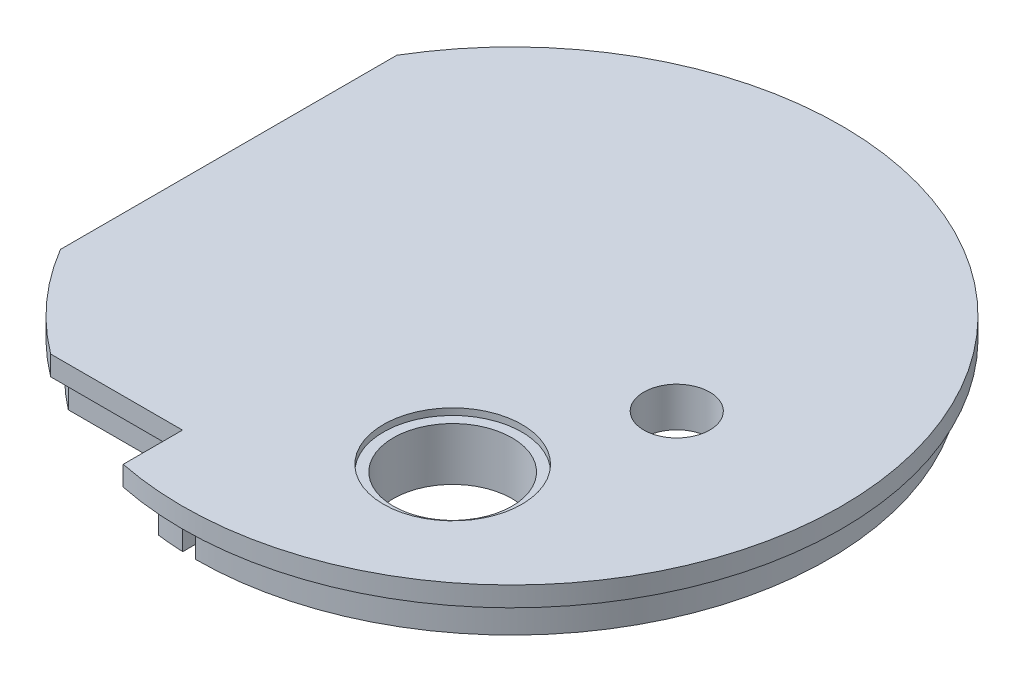
SolidWorks part; units mm, degrees
ref_plane "Front Plane" through (0, 0, 0) normal (0, 0, 1) x (1, 0, 0)
ref_plane "Top Plane" through (0, 0, 0) normal (0, 1, 0) x (1, 0, 0)
ref_plane "Right Plane" through (0, 0, 0) normal (1, 0, 0) x (0, 0, -1)
sketch "Sketch1" plane through (0, 0, 0) normal (0, 1, 0) x (1, 0, 0)
  line L0 (-43, 25.5147) -> (-43, -25.5147)
  line L1 (-30, -40) -> (-10, -40)
  line L2 (-10, -40) -> (-10, -48.9898)
  arc A0 (-43, -25.5147) -> (-30, -40) centre (0, 0) ccw
  arc A1 (-10, -48.9898) -> (-43, 25.5147) centre (0, 0) ccw
  dimension "D1" = 100
  dimension "D2" = 43
  dimension "D3" = 40
  dimension "D4" = 10
extrude "Boss-Extrude1" add sketch "Sketch1" along normal blind 3
sketch "Sketch2" plane through (0, 0, 0) normal (0, -1, 0) x (1, 0, 0)
  line L0 (-40.9781, 24.9959) -> (-40.9781, -24.9959)
  line L1 (-38.9781, 24.4276) -> (-38.9781, -24.4276)
  line L2 (-29.3258, 38) -> (-8, 38)
  line L4 (-28.6356, 36) -> (-8, 36)
  line L7 (-30, 40) -> (-10, 40) construction
  line L8 (-6, 45.607) -> (-6, 47.6235)
  line L10 (-8, -45.299) -> (-8, -47.3286)
  line L11 (-8, 38) -> (-8, 36)
  line L12 (-6, -45.607) -> (-6, -47.6235)
  line L13 (-2, 45.9565) -> (-2, 47.9583)
  line L14 (0, 46) -> (0, 48)
  line L15 (0, -46) -> (0, -48)
  line L16 (-2, -45.9565) -> (-2, -47.9583)
  arc A0 (-40.9781, -24.9959) -> (-8, -47.3286) centre (0, 0) ccw
  arc A1 (-38.9781, -24.4276) -> (-8, -45.299) centre (0, 0) ccw
  arc A2 (-29.3258, 38) -> (-40.9781, 24.9959) centre (0, 0) ccw
  arc A3 (-28.6356, 36) -> (-38.9781, 24.4276) centre (0, 0) ccw
  arc A4 (-2, 45.9565) -> (-6, 45.607) centre (0, 0) ccw
  arc A5 (-2, 47.9583) -> (-6, 47.6235) centre (0, 0) ccw
  arc A7 (-6, -45.607) -> (-2, -45.9565) centre (0, 0) ccw
  arc A8 (-6, -47.6235) -> (-2, -47.9583) centre (0, 0) ccw
  arc A9 (0, -48) -> (0, 48) centre (0, 0) ccw
  arc A10 (0, -46) -> (0, 46) centre (0, 0) ccw
  dimension "D1" = 96
  dimension "D2" = 92
  dimension "D3" = 2
  dimension "D4" = 2
  dimension "D7" = 2
extrude "Boss-Extrude2" add sketch "Sketch2" along normal blind 5
sketch "Sketch3" plane through (0, 0, 0) normal (0, -1, 0) x (1, 0, 0)
  line L0 (0, 0) -> (0, 55.6034) construction
  line L1 (0, 0) -> (17.6812, 0) construction
  circle A0 centre (25, 0) radius 5
  circle A1 centre (15, 24) radius 9
  dimension "D2" = 10
  dimension "D5" = 18
  dimension "D1" = 25
  dimension "D3" = 15
  dimension "D4" = 24
extrude "Cut-Extrude1" cut sketch "Sketch3" against normal blind 3
sketch "Sketch4" plane through (0, 0, 0) normal (0, -1, 0) x (1, 0, 0)
  circle A0 centre (25, 0) radius 8
  circle A1 centre (25, 0) radius 9
  circle A2 centre (25, 0) radius 5
  circle A3 centre (25, 0) radius 6
  dimension "D1" = 16
  dimension "D2" = 18
  dimension "D3" = 10
  dimension "D4" = 12
extrude "Boss-Extrude3" add sketch "Sketch4" along normal blind 3 contours A0 | A1
extrude "Boss-Extrude4" add sketch "Sketch4<3>" along normal blind 3 contours A2 | A3
sketch "Sketch4<3>" plane through (0, 0, 0) normal (0, -1, 0) x (1, 0, 0) same geometry as "Sketch4"
sketch "Sketch6" plane through (0, 0, 0) normal (0, -1, 0) x (1, 0, 0)
  circle A0 centre (15, 24) radius 9
  circle A1 centre (15, 24) radius 10.5
  dimension "D1" = 21
extrude "Boss-Extrude5" add sketch "Sketch6" along normal blind 6
sketch "Sketch7" plane through (0, 3, 0) normal (0, 1, 0) x (1, 0, 0)
  circle A0 centre (15, -24) radius 10.5
  circle A1 centre (15, -24) radius 9
  dimension "D1" = 21
  dimension "D2" = 18
extrude "Cut-Extrude2" cut sketch "Sketch7" against normal blind 1
